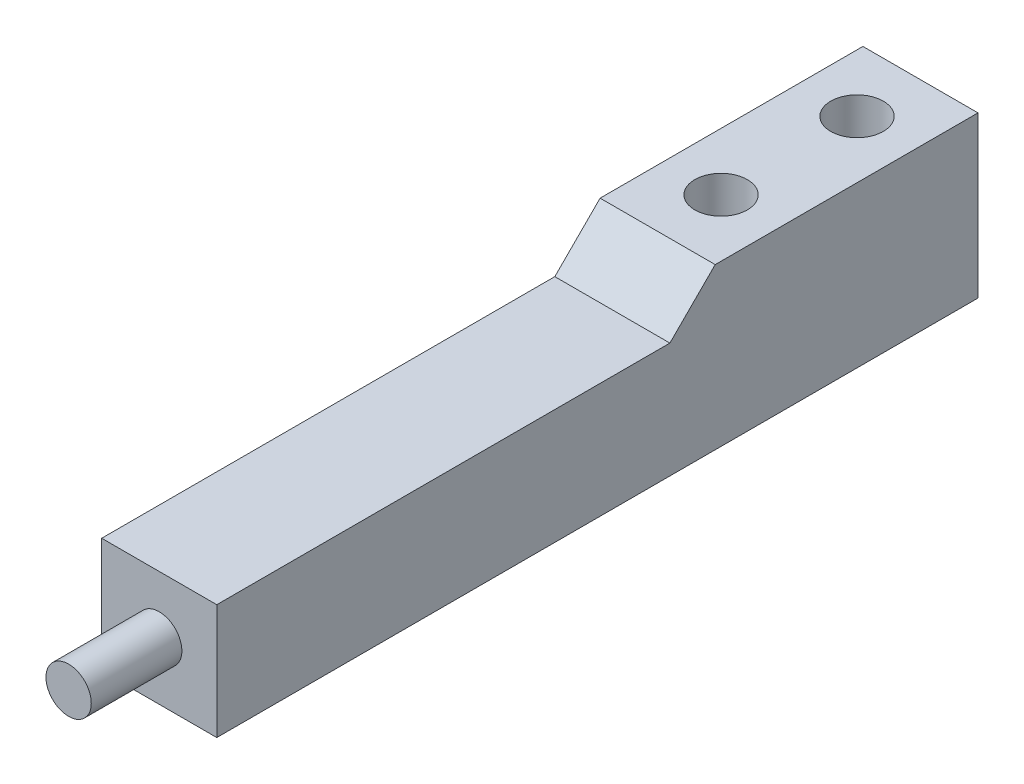
SolidWorks part; units mm, degrees
ref_plane "Front Plane" through (0, 0, 0) normal (0, 0, 1) x (1, 0, 0)
ref_plane "Top Plane" through (0, 0, 0) normal (0, 1, 0) x (1, 0, 0)
ref_plane "Right Plane" through (0, 0, 0) normal (1, 0, 0) x (0, 0, -1)
sketch "Sketch2" plane through (0, 0, 0) normal (0, 1, 0) x (1, 0, 0)
  line L1 (-6.35, -42) -> (6.35, -42)
  line L2 (-6.35, -42) -> (-6.35, 42)
  line L3 (-6.35, 42) -> (6.35, 42)
  line L4 (6.35, -42) -> (6.35, 42)
  line L5 (-6.35, -42) -> (6.35, 42) construction
  line L6 (-6.35, 42) -> (6.35, -42) construction
  point P0 (0, 0)
  dimension "D1" = 84
  dimension "D2" = 12.7
extrude "Boss-Extrude1" add sketch "Sketch2" along normal blind 12.7
sketch "Sketch5" plane through (0, 12.7, 0) normal (0, 1, 0) x (1, 0, 0)
  line L0 (6.35, 42) -> (-6.35, 42) construction
  line L2 (-6.35, 42) -> (6.35, 42)
  line L3 (-6.35, 42) -> (-6.35, 13)
  line L4 (-6.35, 13) -> (6.35, 13)
  line L5 (6.35, 42) -> (6.35, 13)
  point P7 (0, 13)
  dimension "D1" = 12.7
  dimension "D2" = 29
extrude "Boss-Extrude2" add sketch "Sketch5" along normal blind 5
hole_wizard "CBORE for M5 SHCS1" positions "Sketch3" profile "Sketch4" counterbore size "M5" standard "ANSI Metric" end condition through all
sketch "Sketch3" plane through (0, 0, 0) normal (0, -1, 0) x (-1, 0, 0)
  line L0 (0, 35) -> (0, 20) construction
  line L1 (0, -20) -> (0, -35) construction
  line L2 (0, 20) -> (0, -20) construction
  circle A0 centre (0, -20) radius 2.5 construction
  circle A1 centre (0, -35) radius 2.5 construction
  point P0 (0, 35)
  point P2 (0, 20)
  point P28 (0, 0)
  dimension "D2" = 5
  dimension "D1" = 15
  dimension "D3" = 15
  dimension "D4" = 40
sketch "Sketch4" plane through (0, 0, -35) normal (1, 0, 0) x (0, 0, -1)
  line L0 (0, 0) -> (0, 17.7)
  line L1 (0, 17.7) -> (2.9, 17.7)
  line L3 (2.9, 17.7) -> (2.9, 5)
  line L4 (5, 5) -> (2.9, 5)
  line L5 (5, 5) -> (5, 0.021)
  line L6 (5, 0.021) -> (5.025, 0)
  line L7 (5.025, 0) -> (0, 0)
  line L8 (-5, 0.021) -> (-5.025, 0) construction
  line L11 (0, -6.35) -> (0, 107.95) construction
  dimension "Thru Hole Dia." = 5.8
  dimension "Thru Hole Depth" = 17.7
  dimension "C'Bore Dia." = 10
  dimension "C'Bore Depth" = 5
  dimension "Near C'Sink Dia." = 10.05
  dimension "Near C'Sink Angle" = 100
chamfer "Chamfer1" distance 5 angle 45 1 edges at (0, 12.7, -13)
sketch "Sketch6" plane through (0, 0, 42) normal (0, 0, 1) x (1, 0, 0)
  line L0 (6.35, 12.7) -> (6.35, 0) construction
  circle A0 centre (0, 6.35) radius 2.5
  point P6 (6.35, 6.35)
  dimension "D1" = 5
extrude "Boss-Extrude3" add sketch "Sketch6" along normal blind 10
